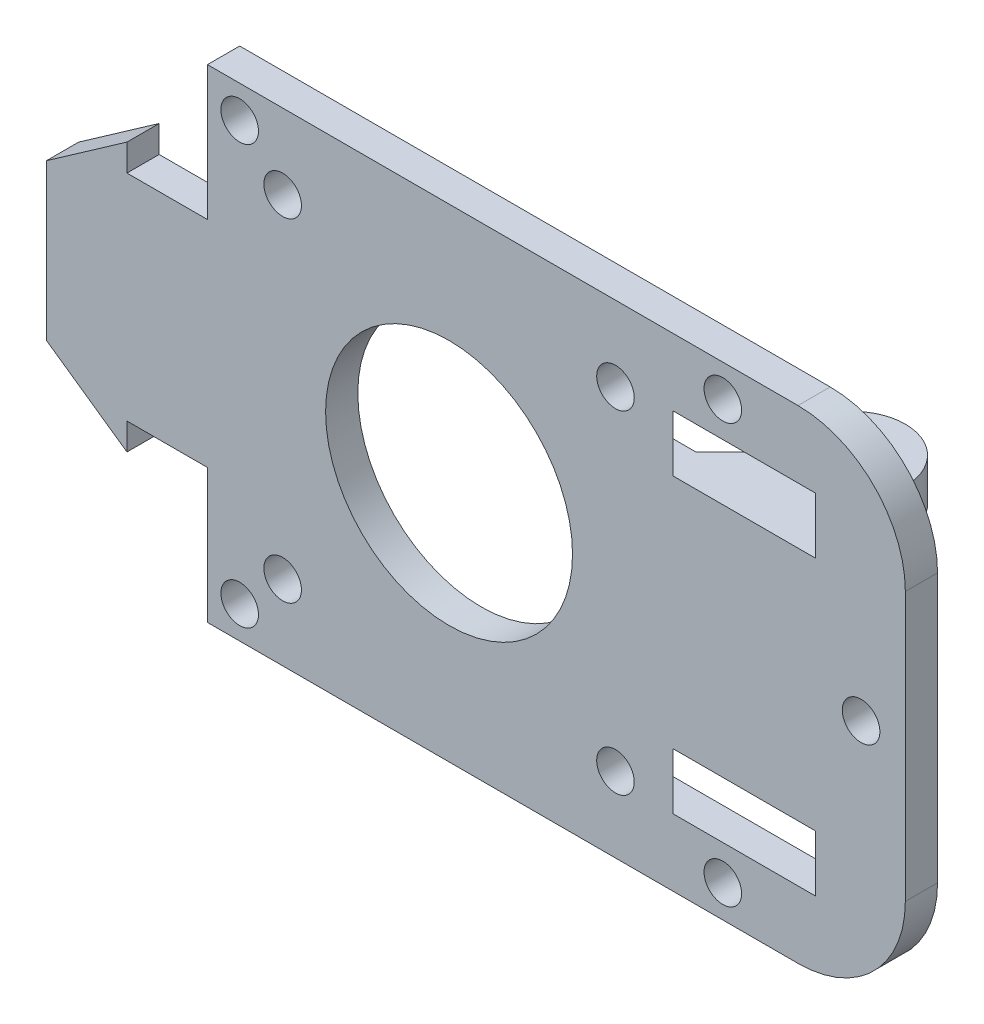
SolidWorks part; units mm, degrees
ref_plane "Front Plane" through (0, 0, 0) normal (0, 0, 1) x (1, 0, 0)
ref_plane "Top Plane" through (0, 0, 0) normal (0, 1, 0) x (1, 0, 0)
ref_plane "Right Plane" through (0, 0, 0) normal (1, 0, 0) x (0, 0, -1)
sketch "Sketch1" plane through (0, 0, 0) normal (0, 0, 1) x (1, 0, 0)
  line L1 (-44.437, 19.3432) -> (20.563, 19.3432)
  line L2 (-44.437, 19.3432) -> (-44.437, -25.6568)
  line L3 (-44.437, -25.6568) -> (20.563, -25.6568)
  line L4 (20.563, 19.3432) -> (20.563, -25.6568)
  dimension "D1" = 65
  dimension "D2" = 45
extrude "Boss-Extrude1" add sketch "Sketch1" along normal blind 3
fillet "Fillet4" radius 10 2 edges at (20.563, -25.6568, 1.5) (20.563, 19.3432, 1.5)
sketch "Sketch8" plane through (0, 0, 0) normal (0, 0, -1) x (-1, 0, 0)
  line L0 (44.437, 19.3432) -> (44.437, -25.6568) construction
  line L1 (44.437, 9.3432) -> (59.437, 9.3432) construction
  line L2 (44.437, 9.3432) -> (44.437, -15.6568) construction
  line L3 (44.437, -15.6568) -> (59.437, -15.6568) construction
  line L4 (59.437, 9.3432) -> (59.437, -15.6568) construction
  line L5 (-10.563, 19.3432) -> (44.437, 19.3432) construction
  line L6 (44.437, -25.6568) -> (-10.563, -25.6568) construction
  line L7 (51.937, 9.3432) -> (51.937, -15.6568) construction
  line L8 (44.437, 6.8432) -> (51.937, 6.8432)
  line L9 (44.437, -13.1568) -> (51.937, -13.1568)
  line L10 (51.937, -15.6568) -> (59.437, -10.4053)
  line L11 (51.937, 9.3432) -> (59.437, 4.0916)
  line L12 (44.437, 6.8432) -> (44.437, -13.1568)
  line L13 (51.937, 9.3432) -> (51.937, 6.8432)
  line L14 (51.937, -13.1568) -> (51.937, -15.6568)
  line L15 (59.437, 4.0916) -> (59.437, -10.4053)
  dimension "D1" = 10
  dimension "D2" = 10
  dimension "D3" = 15
  dimension "D4" = 2.5
  dimension "D5" = 2.5
  dimension "D6" = 55
  dimension "D7" = 55
extrude "Boss-Extrude4" add sketch "Sketch8" against normal blind 3 contours L11 L15 L10 L14 L9 L12 L8 L13
sketch "Sketch2" plane through (0, 0, 0) normal (0, 0, -1) x (-1, 0, 0)
  line L0 (-10.563, 3.8432) -> (-10.563, 7.8432)
  line L5 (-0.563, -10.1568) -> (-10.563, -10.1568) construction
  line L6 (-0.563, -10.1568) -> (-0.563, 3.8432) construction
  line L7 (-0.563, 3.8432) -> (-10.563, 3.8432) construction
  line L8 (-10.563, -10.1568) -> (-10.563, 3.8432) construction
  line L9 (-10.563, 7.8432) -> (-0.563, 7.8432)
  line L10 (-20.563, -3.1568) -> (70.0438, -3.1568) construction
  line L11 (-20.563, -15.6568) -> (-20.563, 9.3432) construction
  line L12 (-0.563, 7.8432) -> (-0.563, 3.8432)
  line L13 (-0.563, 3.8432) -> (-10.563, 3.8432)
  line L14 (-0.563, -14.1568) -> (-0.563, -10.1568)
  line L15 (-10.563, -14.1568) -> (-0.563, -14.1568)
  line L16 (-10.563, -10.1568) -> (-10.563, -14.1568)
  line L17 (-0.563, -10.1568) -> (-10.563, -10.1568)
  dimension "D1" = 14
  dimension "D2" = 10
  dimension "D4" = 10
  dimension "D5" = 4
sketch "Sketch9" plane through (0, 0, 0) normal (0, 0, -1) x (-1, 0, 0)
  line L0 (-3.563, -3.1568) -> (-3.563, 24.531) construction
  line L1 (-20.563, -3.1568) -> (70.0438, -3.1568) construction
  line L2 (-20.563, -15.6568) -> (-20.563, 9.3432) construction
  line L3 (-3.563, -3.1568) -> (-3.563, -31.0588) construction
  line L4 (-33.9259, -22.6568) -> (64.4679, -22.6568) construction
  line L11 (44.437, -25.6568) -> (-10.563, -25.6568) construction
  line L12 (41.437, 30.7387) -> (41.437, -37.8284) construction
  line L13 (44.437, 19.3432) -> (44.437, 6.8432) construction
  line L14 (-26.3067, -3.1568) -> (68.9404, -3.1568) construction
  circle A0 centre (-16.44, -3.1568) radius 1.75
  circle A1 centre (-3.563, -22.6568) radius 1.75
  circle A2 centre (41.437, -22.6568) radius 1.75
  circle A3 centre (41.437, 16.3432) radius 1.75
  circle A4 centre (-3.563, 16.3432) radius 1.75
  dimension "D7" = 0
  dimension "D1" = 17
  dimension "D6" = 3
  dimension "D8" = 3
extrude "Cut-Extrude5" cut sketch "Sketch9" against normal blind 5
sketch "Sketch10" plane through (0, 0, 0) normal (0, 0, -1) x (-1, 0, 0)
  line L0 (-10.563, 19.3432) -> (44.437, 19.3432) construction
  line L1 (6.437, 12.3432) -> (37.437, 12.3432) construction
  line L2 (6.437, 12.3432) -> (6.437, -18.6568) construction
  line L3 (6.437, -18.6568) -> (37.437, -18.6568) construction
  line L4 (37.437, 12.3432) -> (37.437, -18.6568) construction
  line L5 (44.437, -13.1568) -> (44.437, -25.6568) construction
  line L6 (6.437, 12.3432) -> (37.437, -18.6568) construction
  line L7 (6.437, -18.6568) -> (37.437, 12.3432) construction
  circle A1 centre (6.437, -18.6568) radius 1.75
  circle A2 centre (37.437, 12.3432) radius 1.75
  circle A3 centre (6.437, 12.3432) radius 1.75
  circle A4 centre (37.437, -18.6568) radius 1.75
  circle A6 centre (21.937, -3.1568) radius 11.5
  dimension "D5" = 23
  dimension "D1" = 31
  dimension "D2" = 31
  dimension "D3" = 7
  dimension "D4" = 7
extrude "Cut-Extrude6" cut sketch "Sketch10" against normal blind 5
extrude "Boss-Extrude5" add sketch "Sketch2" along normal blind 12
sketch "Sketch11" plane through (0, -14.1568, 0) normal (0, -1, 0) x (1, 0, 0)
  line L0 (0.563, -2) -> (10.563, -2) construction
  line L1 (0.563, -12) -> (0.563, 0) construction
  line L2 (10.563, -12) -> (10.563, 0) construction
  line L3 (10.563, 0) -> (0.563, 0) construction
  line L4 (0.563, -2) -> (10.563, -12) construction
  line L5 (10.563, -2) -> (0.563, -12) construction
  circle A1 centre (5.563, -7) radius 1.75
  dimension "D1" = 2
extrude "Cut-Extrude7" cut sketch "Sketch11" against normal blind 22
chamfer "Chamfer3" distance 2.5 angle 45 4 edges at (0.563, -12.1568, 0) (0.563, 5.8432, 0) (10.563, -12.1568, 0) (10.563, 5.8432, 0)
chamfer "Chamfer4" distance 5 angle 45 2 edges at (5.563, -10.1568, 0) (5.563, 3.8432, 0)
fillet "Fillet5" radius 5 4 edges at (0.563, -12.1568, -12) (10.563, -12.1568, -12) (0.563, 5.8432, -12) (10.563, 5.8432, -12)
ref_axis "Axis1" through (5.563, 7.8432, -7) along (0, -1, 0)
ref_plane "Plane1" through (5.563, 0, 0) normal (1, 0, 0) x (0, 0, -1)
sketch "Sketch13" plane through (5.563, 0, 0) normal (1, 0, 0) x (0, 0, -1)
  line L0 (7, 7.8432) -> (7, 3.8432) construction
  line L1 (19, 13.0932) -> (7, 13.0932)
  line L2 (19, 13.0932) -> (19, 7.8432)
  line L3 (19, 7.8432) -> (7, 7.8432)
  line L4 (7, 13.0932) -> (7, 7.8432)
  line L5 (12, 7.8432) -> (7, 7.8432) construction
  dimension "D1" = 5.25
  dimension "D2" = 12
  dimension "D3" = 0
  dimension "D4" = 0
revolve "Cut-Revolve1" cut sketch "Sketch13" angle 360 about axis through (5.563, 7.8432, -7) along (0, -1, 0)
ref_plane "Plane2" through (0, -3.1568, 0) normal (0, 1, 0) x (1, 0, 0)
mirror "Mirror1" about plane through (0, -3.1568, 0) normal (0, 1, 0) of "Cut-Revolve1"
